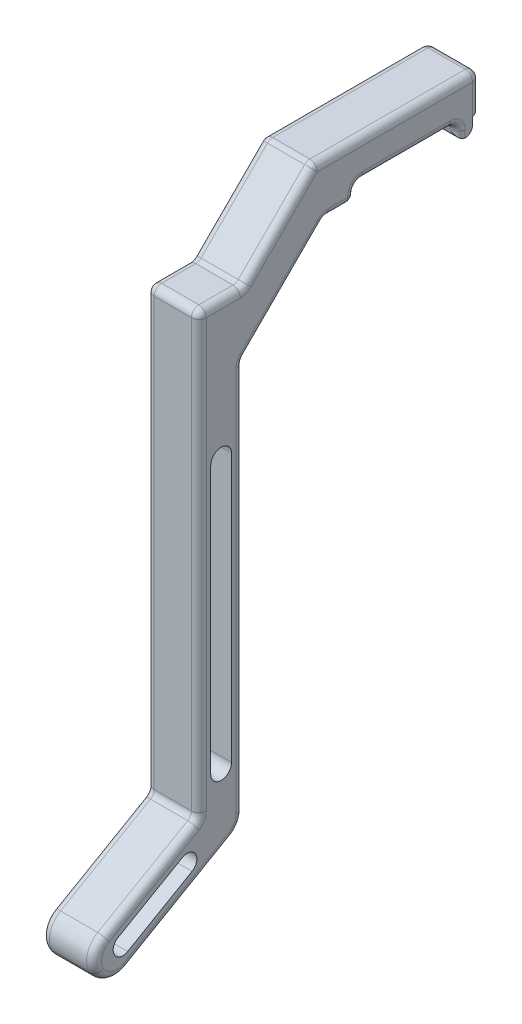
SolidWorks part; units mm, degrees
ref_plane "Front Plane" through (0, 0, 0) normal (0, 0, 1) x (1, 0, 0)
ref_plane "Top Plane" through (0, 0, 0) normal (0, 1, 0) x (1, 0, 0)
ref_plane "Right Plane" through (0, 0, 0) normal (1, 0, 0) x (0, 0, -1)
sketch "Sketch1" plane through (0, 0, 0) normal (1, 0, 0) x (0, 0, -1)
  line L0 (61.1674, 97.4093) -> (61.1674, 91.0593)
  line L1 (-2.3155, -7.3657) -> (20.7814, 5.9693)
  line L2 (13.1614, 10.3687) -> (-6.1255, -0.7666)
  line L3 (61.1674, 91.0593) -> (59.8974, 91.0593)
  line L4 (20.7814, 85.3256) -> (32.865, 97.4093)
  line L5 (-2.3155, -7.3657) -> (-6.1255, -0.7666)
  line L6 (13.1614, 85.3256) -> (13.1614, 10.3687)
  line L7 (32.865, 97.4093) -> (61.1674, 97.4093)
  line L8 (59.8974, 91.0593) -> (59.8974, 88.5193)
  line L9 (59.8974, 88.5193) -> (57.3574, 88.5193)
  line L10 (57.3574, 88.5193) -> (57.3574, 91.0593)
  line L11 (57.3574, 91.0593) -> (39.8314, 91.0593)
  line L12 (39.8314, 91.0593) -> (39.8314, 88.5193)
  line L13 (39.8314, 88.5193) -> (34.7514, 88.5193)
  line L14 (34.7514, 88.5193) -> (20.7814, 74.5493)
  line L15 (20.7814, 74.5493) -> (20.7814, 5.9693)
  line L16 (20.7814, 85.3256) -> (13.1614, 85.3256)
  dimension "D2" = 91.44
  dimension "D3" = 26.67
  dimension "D4" = 1.27
  dimension "D5" = 2.54
  dimension "D6" = 2.54
  dimension "D7" = 7.62
  dimension "D8" = 6.35
  dimension "D9" = 7.62
  dimension "D10" = 17.526
  dimension "D12" = 5.08
  dimension "D13" = 7.62
  dimension "D14" = 7.62
  dimension "D15" = 2.54
extrude "Boss-Extrude1" add sketch "Sketch1" along normal blind 8.89
sketch "Sketch2" plane through (8.89, 0, 0) normal (1, 0, 0) x (0, 0, -1)
  line L0 (1.0044, -2.9559) -> (12.0029, 3.3941)
  line L2 (10.3519, 6.2537) -> (-0.6466, -0.0963)
  line L3 (13.1614, 10.3687) -> (-6.1255, -0.7666) construction
  line L4 (1.0044, -2.9559) -> (4.2604, -1.6233)
  line L5 (-6.1255, -0.7666) -> (-2.3155, -7.3657) construction
  arc A0 (10.3519, 6.2537) -> (12.0029, 3.3941) centre (11.1774, 4.8239) cw
  arc A1 (1.0044, -2.9559) -> (-0.6466, -0.0963) centre (0.1789, -1.5261) cw
  dimension "D1" = 3.81
  dimension "D2" = 5.08
  dimension "D3" = 3.302
  dimension "D4" = 0
  dimension "D6" = 12.7
extrude "Cut-Extrude1" cut sketch "Sketch2" against normal blind 10.16
sketch "Sketch3" plane through (8.89, 0, 0) normal (1, 0, 0) x (0, 0, -1)
  line L0 (61.1674, 97.4093) -> (32.865, 97.4093) construction
  line L2 (15.1934, 61.8493) -> (15.1934, 16.1293)
  line L4 (18.7494, 61.8493) -> (18.7494, 16.1293)
  line L5 (20.7814, 5.9693) -> (20.7814, 74.5493) construction
  arc A0 (18.7494, 61.8493) -> (15.1934, 61.8493) centre (16.9714, 61.8493) ccw
  arc A1 (18.7494, 16.1293) -> (15.1934, 16.1293) centre (16.9714, 16.1293) cw
  dimension "D1" = 3.556
  dimension "D2" = 45.72
  dimension "D3" = 3.81
  dimension "D4" = 35.56
extrude "Cut-Extrude2" cut sketch "Sketch3" against normal blind 10.16
fillet "Fillet5" radius 1.27 39 edges at (8.89, 89.7893, -57.3574) (0, 89.7893, -57.3574) (8.89, 88.5193, -37.2914) (0, 88.5193, -37.2914) (8.89, 91.0593, -48.5944) (0, 91.0593, -48.5944) (8.89, 4.8011, -3.5179) (0, 4.8011, -3.5179) (0, 91.3675, -26.8232) (8.89, 91.3675, -26.8232) (4.445, 74.5493, -20.7814) (8.89, 81.5343, -27.7664) (4.445, 88.5193, -34.7514) (0, 81.5343, -27.7664) (4.445, 88.5193, -39.8314) (4.445, 91.0593, -39.8314) (4.445, 91.0593, -61.1674) (8.89, 94.2343, -61.1674) (0, 94.2343, -61.1674) (4.445, 97.4093, -61.1674) (8.89, 97.4093, -47.0162) (4.445, 97.4093, -32.865) (0, 97.4093, -47.0162) (4.445, 85.3256, -13.1614) (8.89, 47.8472, -13.1614) (4.445, 10.3687, -13.1614) (0, 47.8472, -13.1614) (4.445, 91.0593, -57.3574) (4.445, 88.5193, -57.3574) (4.445, 88.5193, -59.8974) (0, 85.3256, -16.9714) (8.89, 85.3256, -16.9714) (4.445, 85.3256, -20.7814) (0, -4.0661, 4.2205) (8.89, -4.0661, 4.2205) (8.89, -0.6982, -9.2329) (0, -0.6982, -9.2329) (8.89, 40.2593, -20.7814) (0, 40.2593, -20.7814)
fillet "Fillet4" radius 3.81 9 edges at (4.445, -7.3657, 2.3155) (4.445, -0.7666, 6.1255) (4.445, 5.9693, -20.7814) (0.372, -0.9027, 5.6174) (8.518, -0.9027, 5.6174) (0.372, -6.8576, 2.1794) (8.518, -6.8576, 2.1794) (0.372, 6.1841, -20.4094) (8.518, 6.1841, -20.4094)
